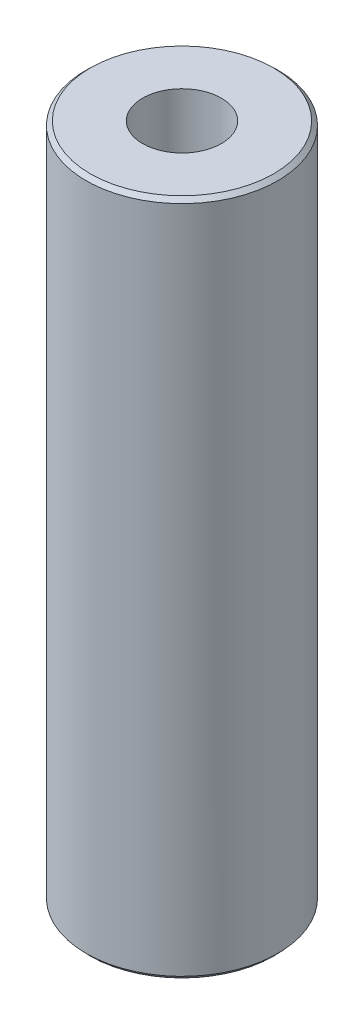
SolidWorks part; units mm, degrees
ref_plane "Front Plane" through (0, 0, 0) normal (0, 0, 1) x (1, 0, 0)
ref_plane "Top Plane" through (0, 0, 0) normal (0, 1, 0) x (1, 0, 0)
ref_plane "Right Plane" through (0, 0, 0) normal (1, 0, 0) x (0, 0, -1)
sketch "Sketch1" plane through (0, 0, 0) normal (0, 1, 0) x (1, 0, 0)
  circle A0 centre (0, 0) radius 45
  dimension "SHAFT_OD" = 90
extrude "Boss-Extrude1" add sketch "Sketch1" along normal blind 317.9142
sketch "Sketch2" plane through (0, 0, 0) normal (0, 1, 0) x (1, 0, 0)
  circle A0 centre (0, 0) radius 18.4986
  dimension "BORE_D" = 36.9971
extrude "Cut-Extrude1" cut sketch "Sketch2" along normal through all
chamfer "Chamfer1" distance 1.8348 angle 46.856 2 edges at (0, 317.9142, 45) (0, 0, 45) first distance on face at (0, 317.9142, 45) first distance on face at (0, 0, 18.4986)
